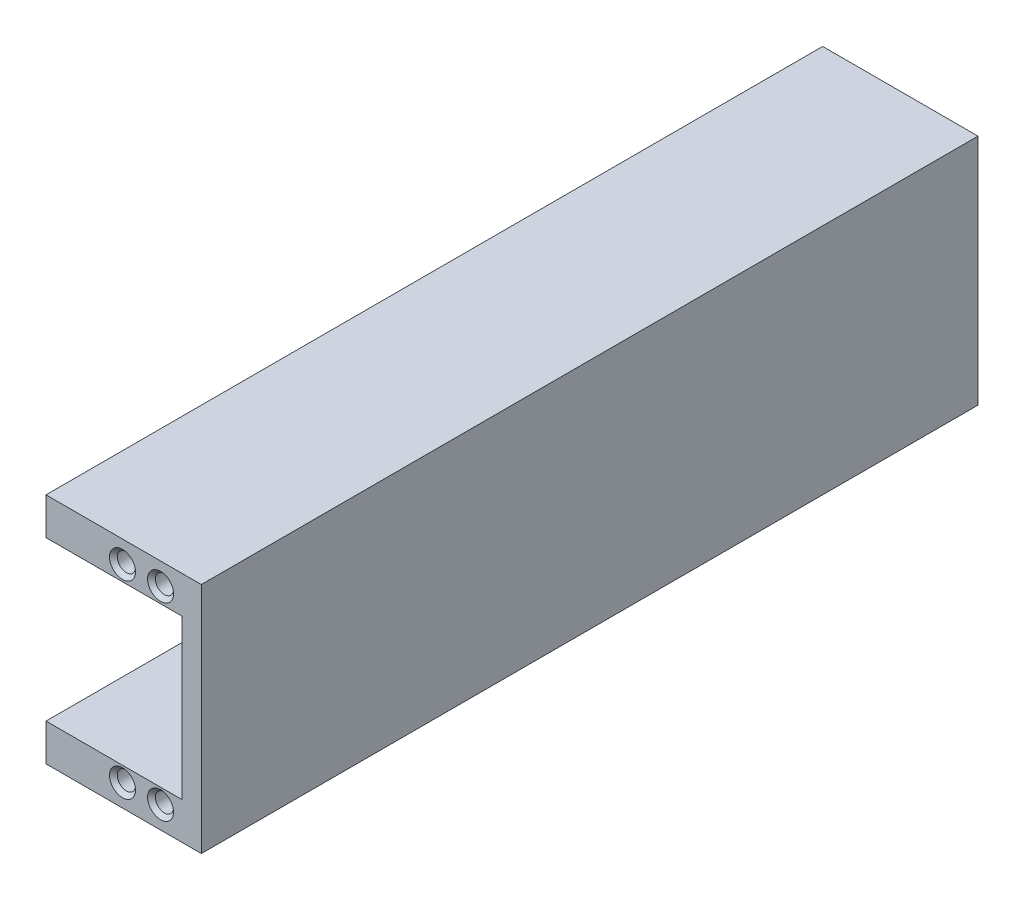
SolidWorks part; units mm, degrees
material "ABS"
ref_plane "Front Plane" through (0, 0, 0) normal (0, 0, 1) x (1, 0, 0)
ref_plane "Top Plane" through (0, 0, 0) normal (0, 1, 0) x (1, 0, 0)
ref_plane "Right Plane" through (0, 0, 0) normal (1, 0, 0) x (0, 0, -1)
sketch "Sketch1" plane through (0, 0, 0) normal (0, 0, 1) x (1, 0, 0)
  line L0 (-20, 30) -> (20, 30)
  line L1 (-20, 30) -> (20, 30) construction
  line L2 (-20, 30) -> (-20, -30) construction
  line L3 (-20, -30) -> (20, -30) construction
  line L4 (20, 30) -> (20, -30) construction
  line L5 (-20, 30) -> (20, -30) construction
  line L6 (-20, -30) -> (20, 30) construction
  line L7 (20, 30) -> (20, -30)
  line L8 (20, -30) -> (-20, -30)
  line L9 (-20, -30) -> (-20, -20.45)
  line L10 (-20, -20.45) -> (15, -20.45)
  line L11 (15, -20.45) -> (15, 20.45)
  line L12 (15, 20.45) -> (-20, 20.45)
  line L13 (-20, 20.45) -> (-20, 30)
  point P0 (0, 0)
  dimension "D1" = 60
  dimension "D2" = 40
  dimension "D3" = 40.9
  dimension "D5" = 5
extrude "Boss-Extrude1" add sketch "Sketch1" along normal blind 200
sketch "Sketch2" plane through (0, 0, 200) normal (0, 0, 1) x (1, 0, 0)
  line L0 (15, 20.45) -> (-5.8, 20.45) construction
  line L1 (-20, 20.45) -> (15, 20.45) construction
  line L2 (4.6, 20.45) -> (4.6, 24.34) construction
  line L3 (4.6, 24.34) -> (9.5, 24.34) construction
  line L4 (15, 20.45) -> (15, -20.45) construction
  line L5 (15, 0) -> (20, 0) construction
  line L6 (20, -30) -> (20, 30) construction
  circle A0 centre (9.5, 24.34) radius 2.35
  circle A1 centre (-0.3, 24.34) radius 2.35
  circle A2 centre (-0.3, -24.34) radius 2.35
  circle A3 centre (9.5, -24.34) radius 2.35
  dimension "D4" = 4.7
  dimension "D1" = 20.8
  dimension "D2" = 3.89
  dimension "D3" = 4.9
extrude "Cut-Extrude1" cut sketch "Sketch2" against normal blind 8
sketch "Sketch3" plane through (0, 0, 0) normal (0, 0, -1) x (-1, 0, 0)
  line L0 (-15, 20.45) -> (5.8, 20.45) construction
  line L1 (20, 20.45) -> (-15, 20.45) construction
  line L2 (-15, 20.45) -> (-15, -20.45) construction
  line L3 (-15, 0) -> (-20, 0) construction
  line L4 (-20, -30) -> (-20, 30) construction
  line L5 (-4.6, 20.45) -> (-4.6, 24.34) construction
  line L6 (-4.6, 24.34) -> (-9.5, 24.34) construction
  circle A0 centre (-9.5, 24.34) radius 2.35
  circle A1 centre (0.3, 24.34) radius 2.35
  circle A2 centre (0.3, -24.34) radius 2.35
  circle A3 centre (-9.5, -24.34) radius 2.35
  dimension "D4" = 4.7
  dimension "D1" = 20.8
  dimension "D2" = 3.89
  dimension "D3" = 4.9
extrude "Cut-Extrude2" cut sketch "Sketch3" against normal blind 8
chamfer "Chamfer1" distance 1 angle 45 8 edges at (-2.65, -24.34, 0) (11.85, -24.34, 0) (7.15, 24.34, 0) (2.05, 24.34, 0) (7.15, -24.34, 200) (2.05, -24.34, 200) (-2.65, 24.34, 200) (11.85, 24.34, 200)
